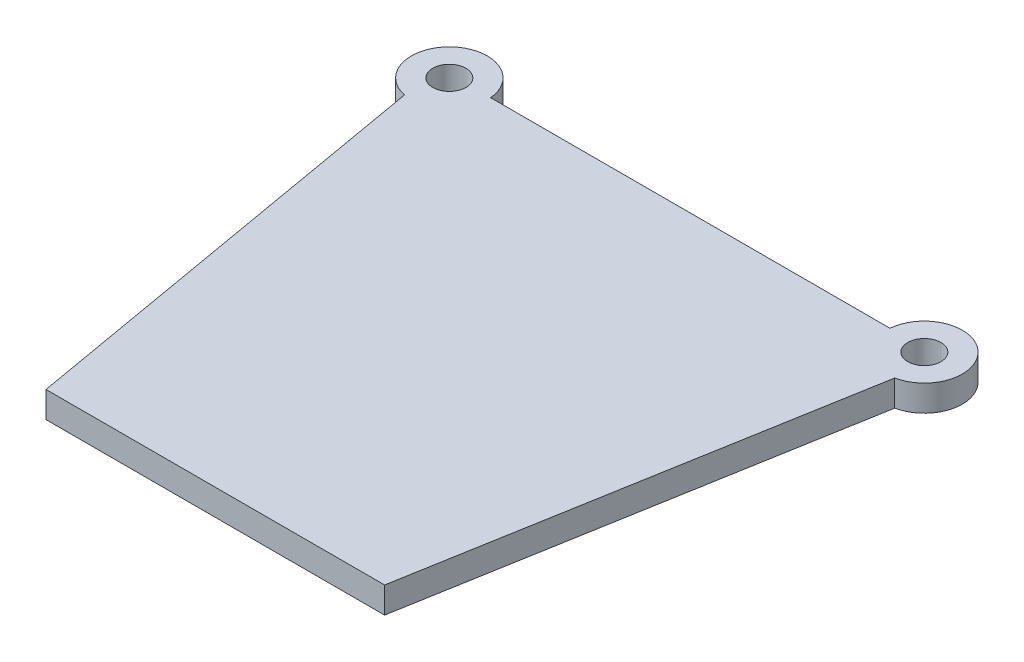
SolidWorks part; units mm, degrees
ref_plane "正面" through (0, 0, 0) normal (0, 0, 1) x (1, 0, 0)
ref_plane "平面" through (0, 0, 0) normal (0, 1, 0) x (1, 0, 0)
ref_plane "右側面" through (0, 0, 0) normal (1, 0, 0) x (0, 0, -1)
sketch "ｽｹｯﾁ1" plane through (0, 0, 0) normal (0, 1, 0) x (1, 0, 0)
  line L0 (0, -64.3386) -> (0, 35.6614) construction
  line L1 (42.0333, 35.6614) -> (-42.0333, 35.6614)
  line L2 (-51.6062, 27.0956) -> (-35.6439, -64.3386)
  line L3 (-35.6439, -64.3386) -> (35.6439, -64.3386)
  line L4 (51.6062, 27.0956) -> (35.6439, -64.3386)
  circle A0 centre (-50, 34.9327) radius 3.5
  arc A1 (-42.0333, 35.6614) -> (-51.6062, 27.0956) centre (-50, 34.9327) ccw
  arc A2 (-51.6062, 27.0956) -> (-42.0333, 35.6614) centre (-50, 34.9327) ccw construction
  arc A3 (51.6062, 27.0956) -> (42.0333, 35.6614) centre (50, 34.9327) cw construction
  arc A4 (42.0333, 35.6614) -> (51.6062, 27.0956) centre (50, 34.9327) cw
  circle A5 centre (50, 34.9327) radius 3.5
  dimension "D1" = 7
  dimension "D2" = 16
  dimension "D3" = 100
  dimension "D4" = 100
extrude "ﾎﾞｽ - 押し出し1" add sketch "ｽｹｯﾁ1" along normal blind 5.5
